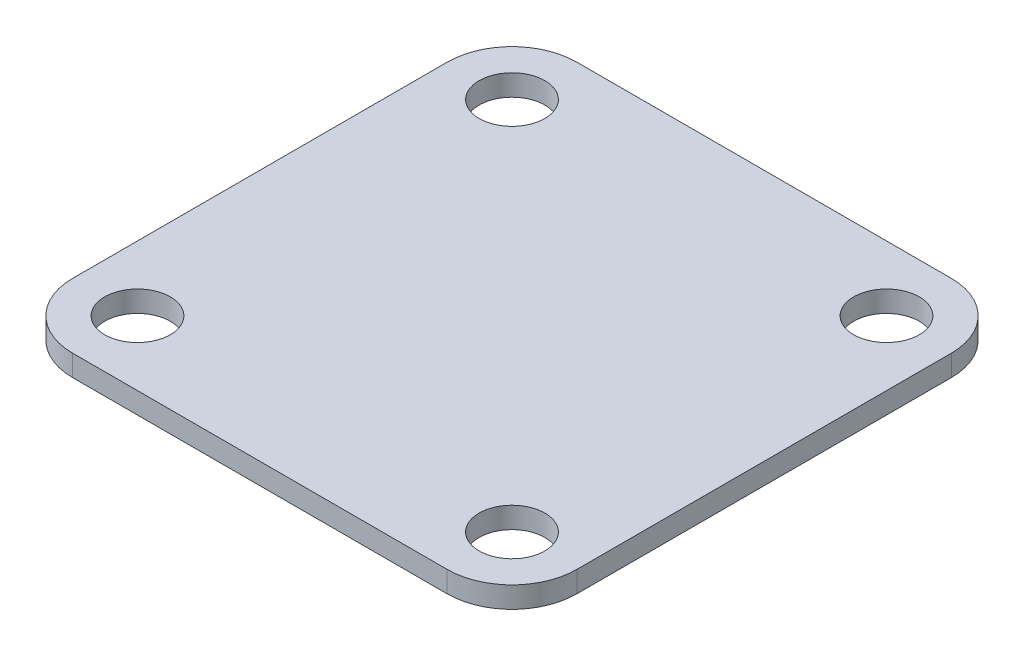
SolidWorks part; units mm, degrees
ref_plane "Front Plane" through (0, 0, 0) normal (0, 0, 1) x (1, 0, 0)
ref_plane "Top Plane" through (0, 0, 0) normal (0, 1, 0) x (1, 0, 0)
ref_plane "Right Plane" through (0, 0, 0) normal (1, 0, 0) x (0, 0, -1)
sketch "Sketch1" plane through (0, 0, 0) normal (0, 1, 0) x (1, 0, 0)
  line L0 (0, 11.9) -> (0, -11.9) construction
  line L1 (-11.9, 11.9) -> (11.9, 11.9)
  line L2 (-11.9, 11.9) -> (-11.9, -11.9)
  line L3 (-11.9, -11.9) -> (11.9, -11.9)
  line L4 (11.9, 11.9) -> (11.9, -11.9)
  line L5 (-11.9, 11.9) -> (11.9, -11.9) construction
  line L6 (-11.9, -11.9) -> (11.9, 11.9) construction
  line L7 (-11.9, 0) -> (11.9, 0) construction
  line L9 (8.84, -8.84) -> (-8.84, -8.84)
  line L10 (8.84, -8.84) -> (8.84, 8.84)
  line L11 (8.84, 8.84) -> (-8.84, 8.84)
  line L12 (-8.84, -8.84) -> (-8.84, 8.84)
  line L13 (8.84, -8.84) -> (-8.84, 8.84) construction
  line L14 (8.84, 8.84) -> (-8.84, -8.84) construction
  circle A0 centre (-8.84, 8.84) radius 1.55
  circle A1 centre (8.84, 8.84) radius 1.55
  circle A2 centre (8.84, -8.84) radius 1.55
  circle A3 centre (-8.84, -8.84) radius 1.55
  circle A4 centre (-8.84, 8.84) radius 3.06
  circle A5 centre (8.84, 8.84) radius 3.06
  circle A6 centre (-8.84, -8.84) radius 3.06
  circle A7 centre (8.84, -8.84) radius 3.06
  point P0 (0, 0)
  point P12 (0, 0)
  dimension "D3" = 3.1
  dimension "D1" = 23.8
  dimension "D2" = 17.68
extrude "Boss-Extrude1" add sketch "Sketch1" along normal blind 1 contours L11 A5 L1 A4 | L11 A4 L12 A0 | L12 A4 L11 A0 | A7 L10 A5 L11 A4 L12 A6 L9 | A5 L11 A1 L10 | A5 L10 A1 L11 | A7 L4 A5 L10 | A7 L10 A2 L9 | L10 A7 L9 A2 | A7 L9 A6 L3 | A6 L12 A3 L9 | L2 A6 L12 A4 | A6 L9 A3 L12 region at (0, 0, -10.4564) region at (-6.7375, 0, -10.9425) region at (-10.4564, 0, 0) region at (10.9425, 0, -10.9425) region at (-7.3201, 0, -7.3201) region at (0, 0, 0) region at (-10.9425, 0, 6.7375) region at (10.4564, 0, 0) region at (7.3201, 0, -7.3201) region at (-7.3201, 0, 7.3201) region at (0, 0, 10.4564) region at (10.9425, 0, 10.9425) region at (7.3201, 0, 7.3201)
